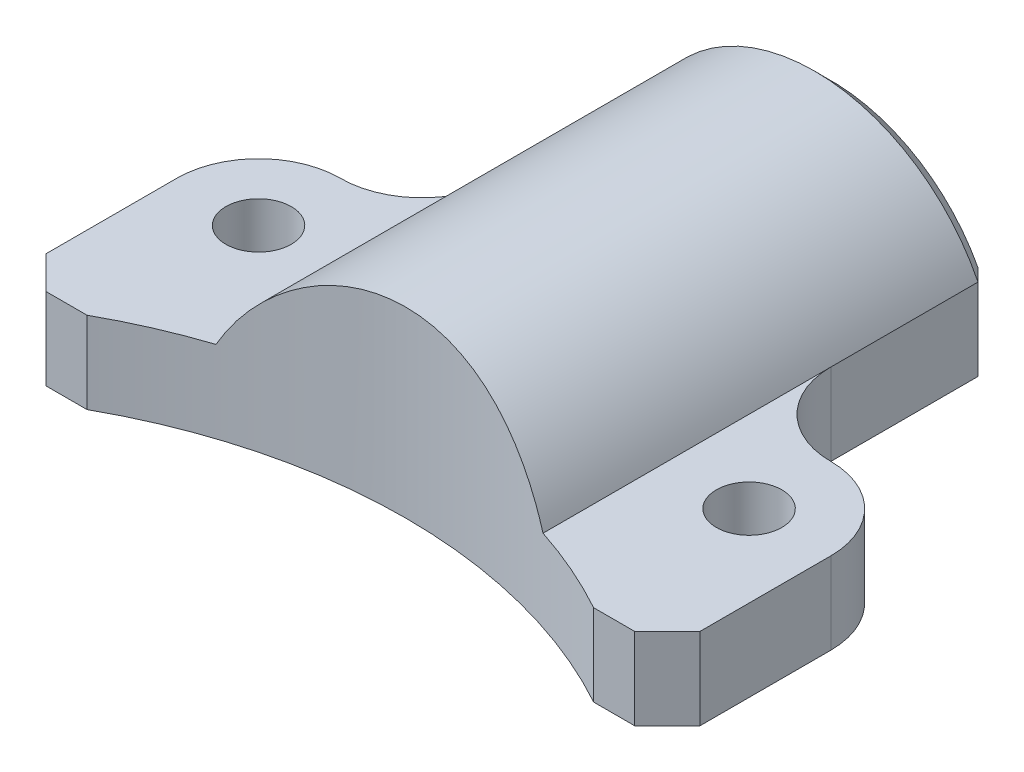
SolidWorks part; units mm, degrees
material "PLA"
ref_plane "Front" through (0, 0, 0) normal (0, 0, 1) x (1, 0, 0)
ref_plane "Top" through (0, 0, 0) normal (0, 1, 0) x (1, 0, 0)
ref_plane "Right" through (0, 0, 0) normal (1, 0, 0) x (0, 0, -1)
sketch "Sketch1" plane through (0, 0, 0) normal (0, 1, 0) x (1, 0, 0)
  line L1 (-20, -15) -> (20, -15)
  line L2 (-20, -15) -> (-20, 15)
  line L3 (-20, 15) -> (20, 15)
  line L4 (20, -15) -> (20, 15)
  line L5 (-20, -15) -> (20, 15) construction
  line L6 (-20, 15) -> (20, -15) construction
  point P0 (0, 0)
  dimension "D1" = 30
  dimension "D2" = 40
extrude "Boss-Extrude1" add sketch "Sketch1" along normal blind 5
sketch "Sketch3" plane through (0, 5, 0) normal (0, 1, 0) x (1, 0, 0)
  line L0 (20, 15) -> (-20, 15) construction
  line L1 (-10, 15) -> (10, 15)
  line L2 (-10, 15) -> (-10, -15)
  line L3 (-10, -15) -> (10, -15)
  line L4 (10, 15) -> (10, -15)
  line L5 (-20, -15) -> (20, -15) construction
  line L6 (0, 0) -> (0, 29.2702) construction
  dimension "D1" = 20
extrude "Boss-Extrude2" add sketch "Sketch3" along normal blind 7.5
sketch "Sketch4" plane through (0, 0, -15) normal (0, 0, -1) x (-1, 0, 0)
  line L1 (-10, 12.5) -> (-10, 5) construction
  line L3 (-10, 5) -> (-10, 21.1803)
  line L4 (-10, 21.1803) -> (10, 21.1803)
  line L5 (10, 21.1803) -> (10, 5)
  line L7 (10, 12.5) -> (10, 5) construction
  circle A0 centre (0, 0) radius 11.1803 construction
  arc A1 (-10, 5) -> (10, 5) centre (0, 0) cw
extrude "Cut-Extrude1" cut sketch "Sketch4" against normal through all
sketch "Sketch5" plane through (0, 5, 0) normal (0, 1, 0) x (1, 0, 0)
  line L1 (-20, 15) -> (-10, 15)
  line L2 (-20, 15) -> (-20, 0)
  line L3 (-20, 0) -> (-10, 0)
  line L4 (-10, 15) -> (-10, 0)
  line L6 (20, 15) -> (10, 15)
  line L7 (20, 15) -> (20, 0)
  line L8 (20, 0) -> (10, 0)
  line L9 (10, 15) -> (10, 0)
  line L10 (10, -15) -> (10, 15) construction
  line L11 (-10, 15) -> (-10, -15) construction
extrude "Cut-Extrude2" cut sketch "Sketch5" against normal through all
sketch "Sketch6" plane through (0, 0, -15) normal (0, 0, -1) x (-1, 0, 0)
  circle A0 centre (0, 0) radius 4
  dimension "D1" = 8
extrude "Cut-Extrude3" cut sketch "Sketch6" against normal blind 20
chamfer "Chamfer1" distance 1 angle 45 4 edges at (0, 11.1803, -15) (0, 4, -15) (10, 2.5, -15) (-10, 2.5, -15)
fillet "Fillet1" radius 5 4 edges at (20, 2.5, 0) (10, 2.5, 0) (-20, 2.5, 0) (-10, 2.5, 0)
sketch "Sketch7" plane through (0, 0, 0) normal (0, -1, 0) x (1, 0, 0)
  circle A0 centre (-15, 5) radius 2
  circle A1 centre (15, 5) radius 2
  arc A2 (15, 0) -> (20, 5) centre (15, 5) ccw construction
  arc A3 (-20, 5) -> (-15, 0) centre (-15, 5) ccw construction
  dimension "D1" = 4
extrude "Cut-Extrude4" cut sketch "Sketch7" against normal through all
chamfer "Chamfer2" distance 2 angle 45 2 edges at (-20, 2.5, 15) (20, 2.5, 15)
sketch "Sketch8" plane through (0, 0, 0) normal (0, -1, 0) x (1, 0, 0)
  line L0 (-4, 5) -> (4, 5) construction
  circle A0 centre (0, 43) radius 32
  dimension "D1" = 64
  dimension "D2" = 38
extrude "Cut-Extrude5" cut sketch "Sketch8" against normal through all
